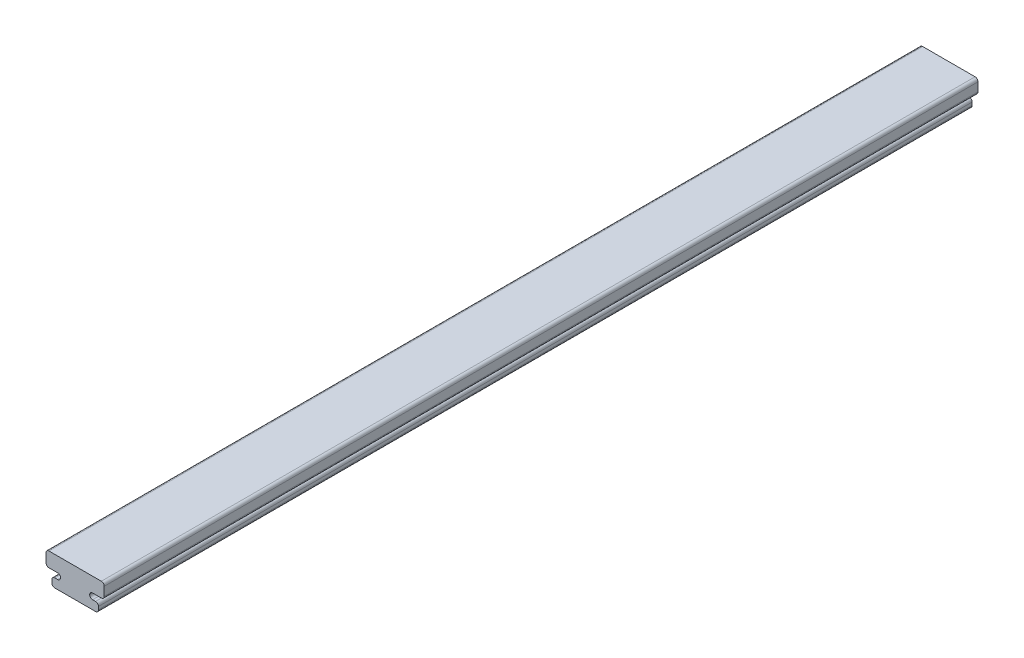
SolidWorks part; units mm, degrees
ref_plane "Front Plane" through (0, 0, 0) normal (0, 0, 1) x (1, 0, 0)
ref_plane "Top Plane" through (0, 0, 0) normal (0, 1, 0) x (1, 0, 0)
ref_plane "Right Plane" through (0, 0, 0) normal (1, 0, 0) x (0, 0, -1)
sketch "Sketch1" plane through (0, 0, 0) normal (0, 0, 1) x (1, 0, 0)
  line L0 (0, 0) -> (-16, 0)
  line L1 (0, 0) -> (0, 3)
  line L2 (-16, 0) -> (-16, 3)
  line L3 (0, 3) -> (-3, 3)
  line L4 (-16, 3) -> (-13, 3)
  line L5 (-3, 3) -> (-3, 5)
  line L6 (-3, 5) -> (-13, 5) construction
  line L7 (-13, 5) -> (-13, 3)
  line L8 (-13, 5) -> (-8, 5) construction
  line L9 (-8, 5) -> (-8, 10) construction
  line L10 (2, 10) -> (-18, 10)
  line L11 (2, 10) -> (2, 5)
  line L12 (2, 5) -> (-3, 5)
  line L13 (-18, 10) -> (-18, 5)
  line L14 (-18, 5) -> (-13, 5)
  dimension "D1" = 16
  dimension "D2" = 3
  dimension "D3" = 2
  dimension "D4" = 5
extrude "Boss-Extrude1" add sketch "Sketch1" along normal blind 300
fillet "Fillet1" radius 1 12 edges at (-13, 5, 150) (-13, 3, 150) (-3, 5, 150) (-3, 3, 150) (0, 0, 150) (0, 3, 150) (-16, 3, 150) (-16, 0, 150) (2, 5, 150) (-18, 5, 150) (2, 10, 150) (-18, 10, 150)
